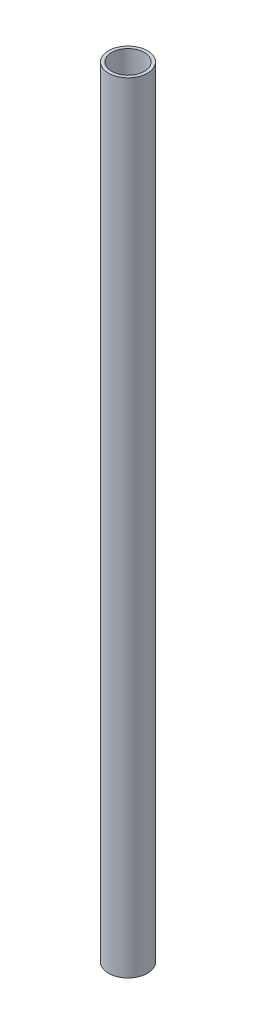
SolidWorks part; units mm, degrees
ref_plane "Front Plane" through (0, 0, 0) normal (0, 0, 1) x (1, 0, 0)
ref_plane "Top Plane" through (0, 0, 0) normal (0, 1, 0) x (1, 0, 0)
ref_plane "Right Plane" through (0, 0, 0) normal (1, 0, 0) x (0, 0, -1)
sketch "Sketch1" plane through (0, 0, 0) normal (0, 1, 0) x (1, 0, 0)
  circle A0 centre (0, 0) radius 12.5
  circle A1 centre (0, 0) radius 10.5
  dimension "D1" = 25
  dimension "D2" = 21
extrude "Boss-Extrude1" add sketch "Sketch1" along normal blind 500
equation "\"D1@Sketch1\" = \"cf_tube_outer_diameter\""
equation "\"D1@Boss-Extrude1\"= \"mid_tube_length\""
equation "\"cf_tube_outer_diameter\"= 25mm"
equation "\"mid_plate_mid_to_top\"= 100mm"
equation "\"mid_plate_mid_to_bottom\"= 30mm"
equation "\"mid_plate_horizontal_spacing\"= 250mm"
equation "\"mid_tube_length\"= 500mm"
equation "\"cf_tube_inner_diameter\"= 21mm"
equation "\"D2@Sketch1\"=\"cf_tube_inner_diameter\""
